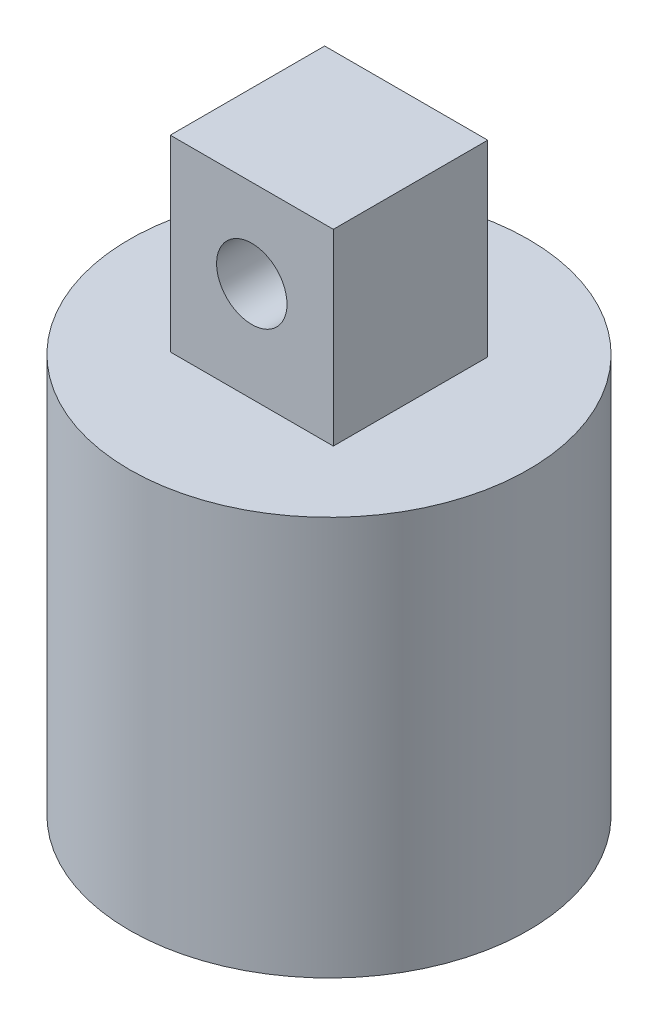
SolidWorks part; units mm, degrees
ref_plane "Front Plane" through (0, 0, 0) normal (0, 0, 1) x (1, 0, 0)
ref_plane "Top Plane" through (0, 0, 0) normal (0, 1, 0) x (1, 0, 0)
ref_plane "Right Plane" through (0, 0, 0) normal (1, 0, 0) x (0, 0, -1)
sketch "Sketch1" plane through (0, 0, 0) normal (0, 1, 0) x (1, 0, 0)
  circle A0 centre (0, 0) radius 8.5
  dimension "D1" = 17
extrude "Boss-Extrude1" add sketch "Sketch1" along normal blind 2
sketch "Sketch2" plane through (0, 2, 0) normal (0, 1, 0) x (1, 0, 0)
  line L1 (-3.4744, -3.2895) -> (3.4744, -3.2895)
  line L2 (-3.4744, -3.2895) -> (-3.4744, 3.2895)
  line L3 (-3.4744, 3.2895) -> (3.4744, 3.2895)
  line L4 (3.4744, -3.2895) -> (3.4744, 3.2895)
  line L5 (-3.4744, -3.2895) -> (3.4744, 3.2895) construction
  line L6 (-3.4744, 3.2895) -> (3.4744, -3.2895) construction
  point P0 (0, 0)
extrude "Boss-Extrude2" add sketch "Sketch2" along normal blind 8
sketch "Sketch3" plane through (0, 0, 3.2895) normal (0, 0, 1) x (1, 0, 0)
  circle A0 centre (0, 6.2484) radius 1.5
  dimension "D1" = 3
extrude "Cut-Extrude1" cut sketch "Sketch3" against normal blind 8
extrude "Boss-Extrude3" add sketch "Sketch1<2>" against normal blind 15
sketch "Sketch1<2>" plane through (0, 0, 0) normal (0, 1, 0) x (1, 0, 0) same geometry as "Sketch1"
sketch "Sketch5" plane through (0, -15, 0) normal (0, -1, 0) x (-1, 0, 0)
  circle A0 centre (0, 0) radius 7
  dimension "D1" = 14
extrude "Cut-Extrude2" cut sketch "Sketch5" against normal blind 15
